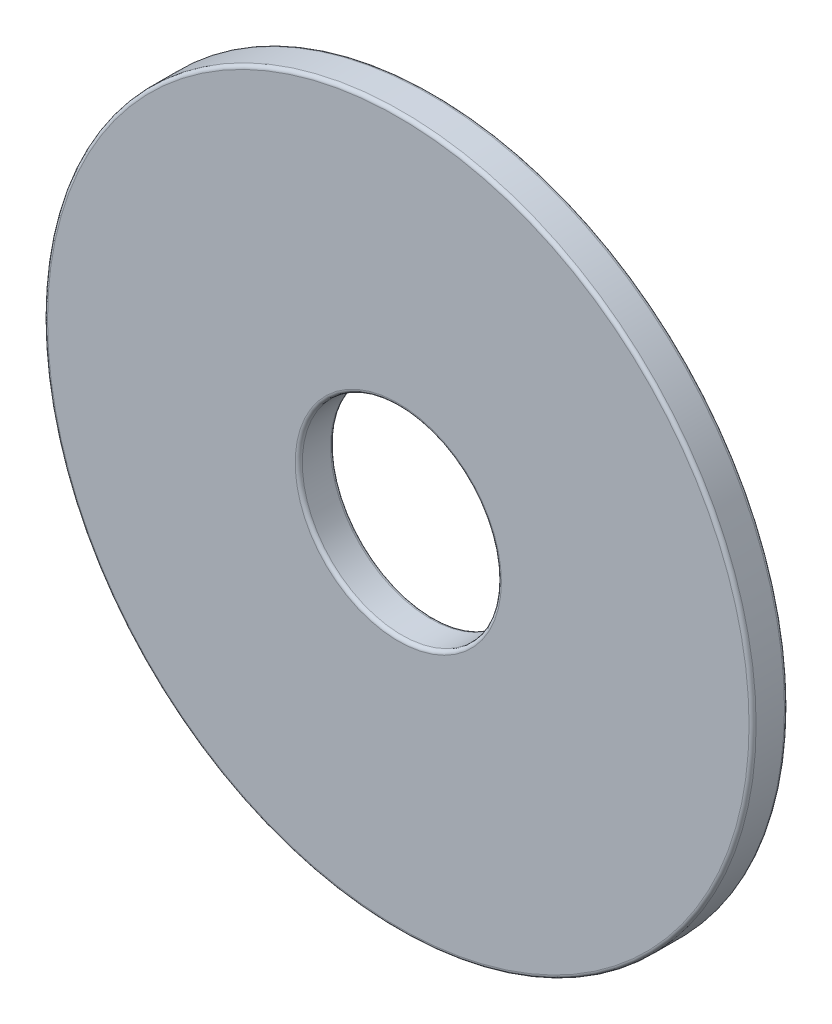
SolidWorks part; units mm, degrees
material "AISI 316 Stainless Steel Sheet (SS)"
ref_plane "Front Plane" through (0, 0, 0) normal (0, 0, 1) x (1, 0, 0)
ref_plane "Top Plane" through (0, 0, 0) normal (0, 1, 0) x (1, 0, 0)
ref_plane "Right Plane" through (0, 0, 0) normal (1, 0, 0) x (0, 0, -1)
sketch "Sketch1" plane through (0, 0, 0) normal (0, 0, 1) x (1, 0, 0)
  circle A0 centre (0, 0) radius 3.5687
  circle A1 centre (0, 0) radius 12.7
  point P4 (0, 12.7)
  point P5 (0, 3.5687)
  point P6 (0, -3.5687)
  point P7 (3.5687, 0)
  point P8 (-3.5687, 0)
  dimension "OD" = 25.4
  dimension "ID" = 7.1374
sketch "Sketch2" plane through (0, 0, 0) normal (1, 0, 0) x (0, 0, -1)
  line L1 (-0.635, 12.7) -> (0.635, 12.7)
  line L2 (-0.635, 12.7) -> (-0.635, -12.7)
  line L3 (-0.635, -12.7) -> (0.635, -12.7)
  line L4 (0.635, 12.7) -> (0.635, -12.7)
  point P4 (0, 12.7)
  point P5 (0.635, 0)
  dimension "Thickness Range" = 1.27
sketch "Sketch3" plane through (0, 0, 0) normal (0, 0, 1) x (1, 0, 0)
  circle A0 centre (0, 0) radius 3.5687 construction
  circle A1 centre (0, 0) radius 12.7 construction
  circle A2 centre (0, 0) radius 3.5687
  circle A3 centre (0, 0) radius 12.7
extrude "Boss-Extrude1" add sketch "Sketch3" against normal up to vertex (0.635 mm away) from vertex up to point (0, 12.7, -0.635) starting at point (0, 12.7, 0.635)
fillet "Fillet1" radius 0.127 4 edges at (3.5687, 0, 0.635) (3.5687, 0, -0.635) (12.7, 0, 0.635) (12.7, 0, -0.635)
equation "\"D1@Fillet1\"=\"Thickness Range@Sketch2\"*.1"
